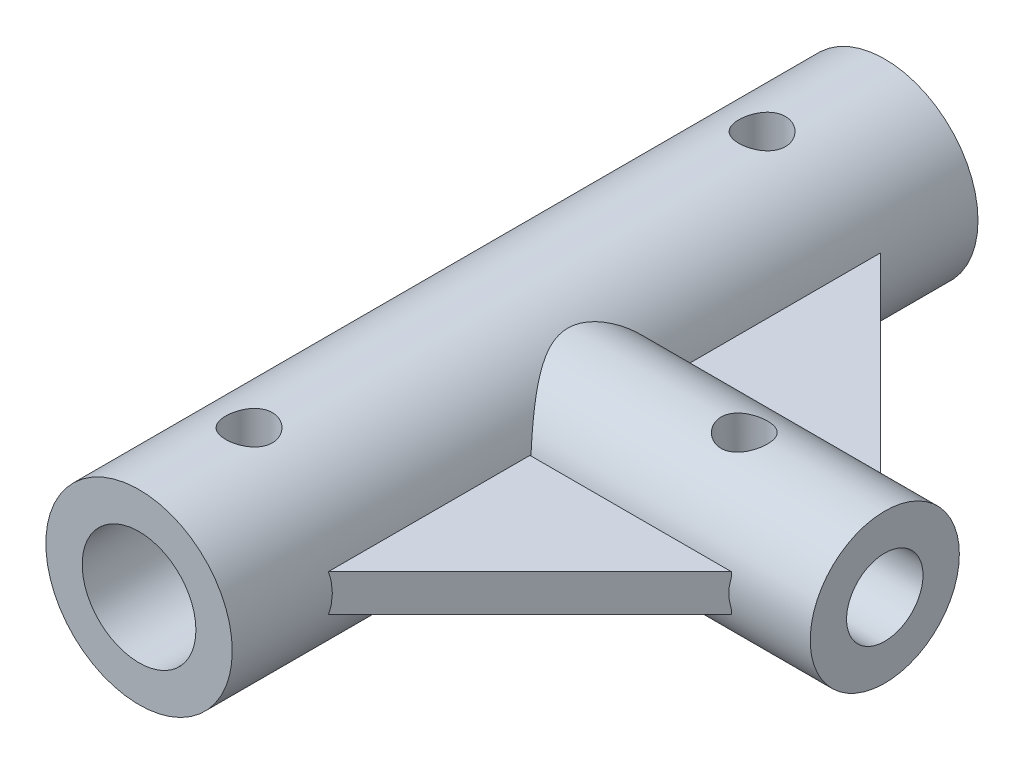
SolidWorks part; units mm, degrees
ref_plane "Front Plane" through (0, 0, 0) normal (0, 0, 1) x (1, 0, 0)
ref_plane "Top Plane" through (0, 0, 0) normal (0, 1, 0) x (1, 0, 0)
ref_plane "Right Plane" through (0, 0, 0) normal (1, 0, 0) x (0, 0, -1)
sketch "Sketch1" plane through (0, 0, 0) normal (0, 0, 1) x (1, 0, 0)
  circle A0 centre (0, 0) radius 5
  circle A1 centre (0, 0) radius 3.05
extrude "Boss-Extrude1" add sketch "Sketch1" along normal blind 20
extrude "Boss-Extrude2" add sketch "Sketch1<2>" against normal blind 20
sketch "Sketch1<2>" plane through (0, 0, 0) normal (0, 0, 1) x (1, 0, 0) same geometry as "Sketch1"
sketch "Sketch2" plane through (0, 0, 0) normal (1, 0, 0) x (0, 0, -1)
  circle A0 centre (0, 0) radius 2.05
  circle A1 centre (0, 0) radius 4
extrude "Boss-Extrude3" add sketch "Sketch2" along normal blind 20
sketch "Sketch3" plane through (20, 0, 0) normal (1, 0, 0) x (0, 0, -1)
  circle A0 centre (0, 0) radius 2.05
extrude "Cut-Extrude1" cut sketch "Sketch3" against normal blind 20
sketch "Sketch4" plane through (0, 0, 20) normal (0, 0, 1) x (1, 0, 0)
  circle A0 centre (0, 0) radius 3.05
extrude "Cut-Extrude2" cut sketch "Sketch4" against normal through all
hole_wizard "M3x0.5 Tapped Hole1" positions "3DSketch1" profile "Sketch5" tap size "M3x0.5" standard "ANSI Metric" end condition up to next
sketch3d "3DSketch1"
  point P0 (12.4888, 3.9999, 0.0232)
sketch "Sketch5" plane through (12.4888, 3.9999, 0.0232) normal (1, 0, 0) x (0, -0.0058, 1)
  line L0 (0, 0) -> (0, 1.95)
  line L1 (0, 1.95) -> (1.25, 1.95)
  line L2 (1.25, 1.95) -> (1.25, 0)
  line L5 (1.25, 0) -> (0, 0)
  line L11 (0, -6.35) -> (0, 107.95) construction
  dimension "Thru Tap Drill Dia." = 2.5
  dimension "Thru Tap Drill Depth" = 1.95
cosmetic thread "Hole Thread1" parameters "D2"=3
hole_wizard "M3x0.5 Tapped Hole2" positions "Sketch6" profile "Sketch7" tap size "M3x0.5" standard "ANSI Metric" end condition up to next
sketch "Sketch6" plane through (0, 0, 0) normal (0, 1, 0) x (1, 0, 0)
  point P0 (0, 13.4176)
  point P2 (0, -14.1007)
sketch "Sketch7" plane through (0, 0, -13.4176) normal (1, 0, 0) x (0, 0, -1)
  line L0 (0, 0) -> (0, 5)
  line L1 (0, 5) -> (1.25, 5)
  line L2 (1.25, 5) -> (1.25, 0)
  line L5 (1.25, 0) -> (0, 0)
  line L11 (0, -6.35) -> (0, 107.95) construction
  dimension "Thru Tap Drill Dia." = 2.5
  dimension "Thru Tap Drill Depth" = 5
cosmetic thread "Hole Thread2" parameters "D2"=3
cosmetic thread "Hole Thread3" parameters "D2"=3
sketch3d "3DSketch2"
  line L0 (0, 0, 20) -> (0, 0, -20) construction
  line L1 (0, 0, 20) -> (0, 0, -20) construction
  line L2 (0, 0, 20) -> (0, 0, -20) construction
  line L3 (0, 0, 20) -> (21.3154, 0, 20) construction
  line L4 (20, 0, 0) -> (20, 0, 4) construction
  line L5 (20, 0, 0) -> (3.05, 0, 0) construction
  line L6 (20, 0, 0) -> (5, 0, 0) construction
  line L7 (5, 0, 15) -> (16, 0, 4)
  line L8 (16, 0, -4) -> (5, 0, -15)
  line L9 (0, 0, -20) -> (5, 0, -20) construction
  line L10 (5, 0, -20) -> (5, 0, 20) construction
  line L11 (20, 0, 0) -> (20, 0, -4) construction
  line L12 (20, 0, -4) -> (14.5819, 0, -4) construction
  line L13 (20, 0, 4) -> (14.5799, 0, 4) construction
  line L14 (16, 0, 4) -> (5, 0, 4)
  line L15 (5, 0, 4) -> (5, 0, 15)
  line L16 (16, 0, -4) -> (5, 0, -4)
  line L17 (5, 0, -4) -> (5, 0, -15)
  circle A0 centre (0, 0, -20) radius 5 construction
  circle A1 centre (0, 0, 20) radius 5 construction
  circle A2 centre (20, 0, 0) radius 4 construction
  point P16 (0, 0, -15)
  point P20 (0, 0, 25)
  point P26 (24, 0, 0)
ref_plane "Plane1" through (0, 0, 0) normal (0, -1, 0) x (-1, 0, 0)
sketch "Sketch11" plane through (0, 0, 0) normal (0, -1, 0) x (-1, 0, 0)
  line L0 (-4.7024, -14.9302) -> (-4.7024, -3.9302)
  line L1 (-4.7024, -3.9302) -> (-15.7024, -3.9302)
  line L2 (-15.7024, -3.9302) -> (-4.7024, -14.9302)
  line L3 (-4.7024, 4.0698) -> (-4.7024, 15.0698)
  line L4 (-4.7024, 15.0698) -> (-15.7024, 4.0698)
  line L5 (-15.7024, 4.0698) -> (-4.7024, 4.0698)
extrude "Boss-Extrude4" add sketch "Sketch11" against normal mid plane 2 separate body
